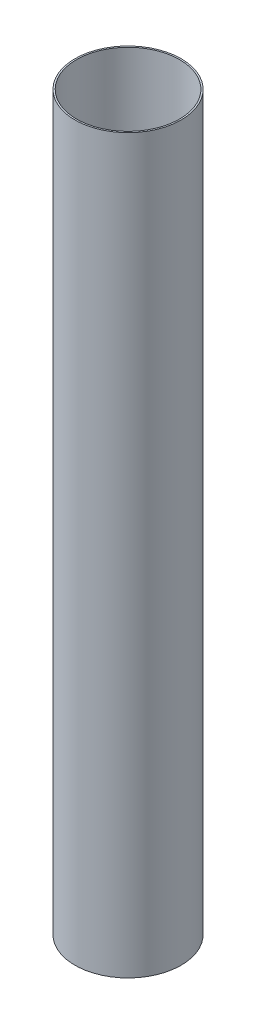
SolidWorks part; units mm, degrees
ref_plane "Front Plane" through (0, 0, 0) normal (0, 0, 1) x (1, 0, 0)
ref_plane "Top Plane" through (0, 0, 0) normal (0, 1, 0) x (1, 0, 0)
ref_plane "Right Plane" through (0, 0, 0) normal (1, 0, 0) x (0, 0, -1)
sketch "Sketch1" plane through (0, 0, 0) normal (0, 1, 0) x (1, 0, 0)
  circle A0 centre (0, 0) radius 65.405
  circle A1 centre (0, 0) radius 63.5
  dimension "D1" = 130.81
  dimension "D2" = 127
extrude "Boss-Extrude1" add sketch "Sketch1" along normal mid plane 901.7
equation "\"iDiameter\"= 5in"
equation "\"oDiameter\"= 5.15in"
equation "\"length\"= 35.5in"
